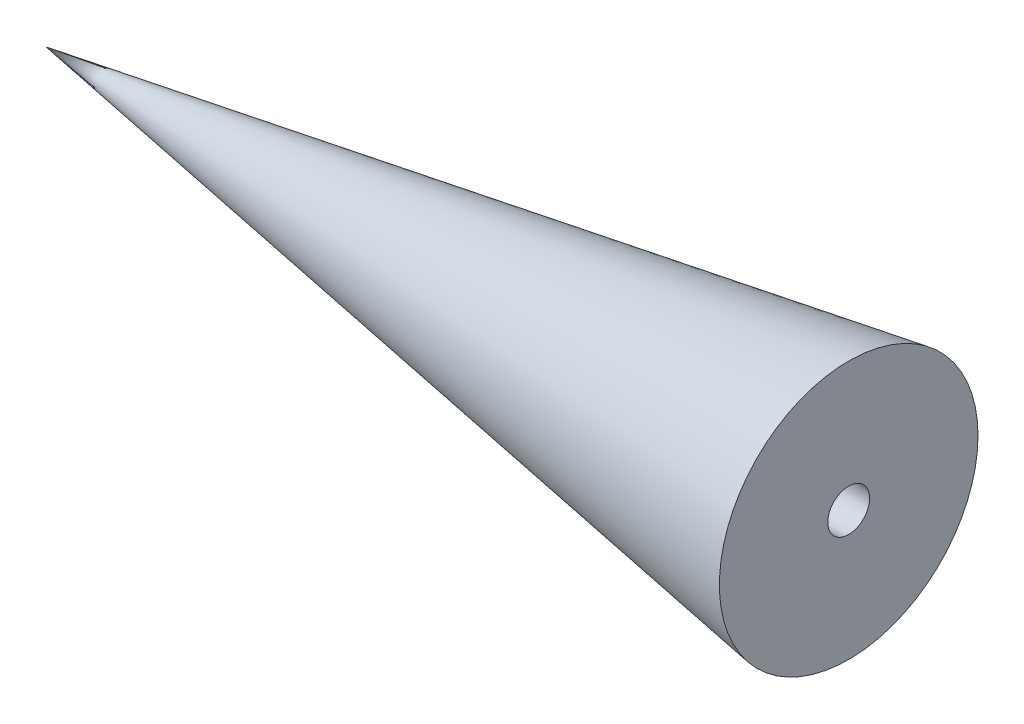
SolidWorks part; units mm, degrees
ref_plane "Płaszczyzna przednia" through (0, 0, 0) normal (0, 0, 1) x (1, 0, 0)
ref_plane "Płaszczyzna górna" through (0, 0, 0) normal (0, 1, 0) x (1, 0, 0)
ref_plane "Płaszczyzna prawa" through (0, 0, 0) normal (1, 0, 0) x (0, 0, -1)
sketch "Sketch1" plane through (0, 0, 0) normal (0, 0, 1) x (1, 0, 0)
  line L1 (0, 0) -> (0, 18.525)
  line L2 (0, 18.525) -> (-115, 0)
  line L3 (0, 0) -> (-115, 0) construction
  line L4 (0, 0) -> (-115, 0)
  dimension "D1" = 115
  dimension "D2" = 18.525
revolve "Revolve1" add sketch "Sketch1" angle 360 about L3
sketch "Sketch2" plane through (0, 0, 0) normal (1, 0, 0) x (0, 0, -1)
  circle A0 centre (0, 0) radius 3
  dimension "D1" = 6
extrude "Cut-Extrude1" cut sketch "Sketch2" against normal blind 40
